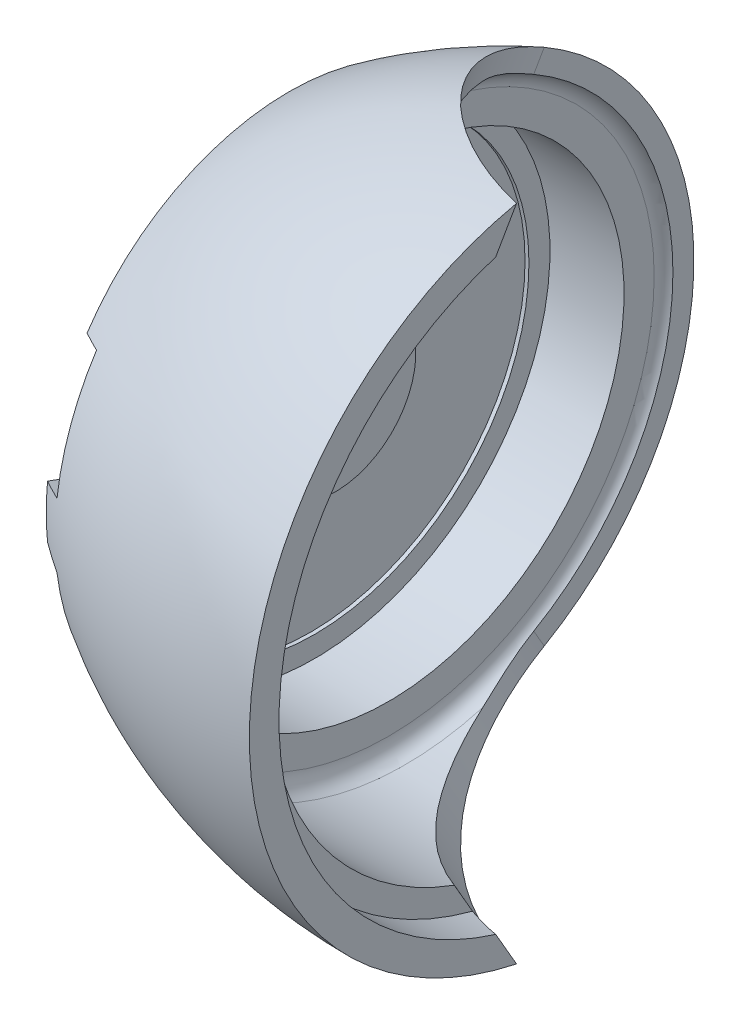
SolidWorks part; units mm, degrees
ref_plane "Front Plane" through (0, 0, 0) normal (0, 0, 1) x (1, 0, 0)
ref_plane "Top Plane" through (0, 0, 0) normal (0, 1, 0) x (1, 0, 0)
ref_plane "Right Plane" through (0, 0, 0) normal (1, 0, 0) x (0, 0, -1)
sketch "Sketch1" plane through (0, 0, 0) normal (0, 0, 1) x (1, 0, 0)
  line L0 (0, -55) -> (0, 55) construction
  line L1 (55, 0) -> (-55, 0) construction
  line L3 (-39.088, 0) -> (-39.088, 12.4)
  line L4 (-39.088, 12.4) -> (-42.39, 12.4)
  line L5 (-42.3, 33.02) -> (-42.3, 36.2585)
  line L7 (-42.988, 0) -> (-39.088, 0)
  line L9 (-30.9, 36.2585) -> (-42.3, 36.2585)
  line L10 (-46.2, 37.409) -> (-46.2, 8.59)
  line L14 (-30.9, 43.434) -> (-5.91, 43.434)
  line L17 (-46.2, 8.59) -> (-42.988, 8.59)
  line L18 (-42.988, 8.59) -> (-42.988, 0)
  line L19 (-42.3, 33.02) -> (-42.9, 33.02)
  line L20 (-42.9, 33.02) -> (-42.9, 12.4)
  line L21 (-42.9, 12.4) -> (-42.39, 12.4)
  line L22 (-30.9, 36.2585) -> (-30.9, 43.434)
  line L23 (-0.51, 51.8144) -> (-0.51, 47.244)
  line L24 (-0.51, 47.244) -> (-5.91, 47.244)
  line L25 (-5.91, 47.244) -> (-5.91, 43.434)
  arc A1 (-0.51, 51.8144) -> (-46.2, 37.409) centre (0, -29.464) ccw
  dimension "D1" = 81.28
  dimension "D2" = 43.434
  dimension "D3" = 46.2
  dimension "D4" = 12.4
  dimension "D5" = 7.112
  dimension "D6" = 11.4
  dimension "D7" = 29.464
  dimension "D8" = 3.9
  dimension "D9" = 36.2585
  dimension "D10" = 5.4
  dimension "D11" = 0.51
  dimension "D12" = 3.9
  dimension "D13" = 3.81
  dimension "D14" = 0.6
  dimension "D15" = 33.02
  dimension "D16" = 3.81
revolve "Revolve1" add sketch "Sketch1" angle 360 about L7
fillet "Fillet1" radius 2.54 1 edges at (-30.9, 0, 43.434)
ref_axis "Axis1" through (-48.7934, 0, 0) along (1, 0, 0)
ref_plane "Plane3" through (0, 0, 0) normal (0, -0.866, 0.5) x (1, 0, 0)
sketch "Sketch9" plane through (0, 0, 0) normal (0, -0.866, 0.5) x (1, 0, 0)
  line L0 (-48.7934, 0) -> (18.8214, 0) construction
  line L2 (0, -53.5869) -> (0, 53.5869) construction
  circle A0 centre (5.08, 0) radius 35.052
  dimension "D1" = 70.104
  dimension "D2" = 5.08
extrude "Cut-Extrude4" cut sketch "Sketch9" against normal blind 57.912
mirror "Mirror3" about plane through (0, 0, 0) normal (0, 1, 0) of "Cut-Extrude4"
ref_plane "Plane4" through (0, 0, 0) normal (0, -0.5, -0.866) x (1, 0, 0)
sketch "Sketch10" plane through (0, 0, 0) normal (0, -0.5, -0.866) x (1, 0, 0)
  line L1 (-29.972, -27.8884) -> (28.0432, -27.8884)
  line L2 (-29.972, -27.8884) -> (-29.972, -56.7179)
  line L3 (-29.972, -56.7179) -> (28.0432, -56.7179)
  line L4 (28.0432, -27.8884) -> (28.0432, -56.7179)
  line L5 (-29.972, -42.8569) -> (-29.972, -46.0881) construction
revolve "Cut-Revolve2" cut sketch "Sketch10" angle 120 about axis through (-48.7934, 0, 0) along (1, 0, 0) reverse direction yes
ref_plane "Plane5" through (0, 0, 0) normal (0, -0.342, -0.9397) x (1, 0, 0)
sketch "Sketch11" plane through (0, 0, 0) normal (0, -0.342, -0.9397) x (1, 0, 0)
  line L1 (-42.3, 8.89) -> (-47.38, 8.89)
  line L2 (-42.3, 8.89) -> (-42.3, -8.89)
  line L3 (-42.3, -8.89) -> (-47.38, -8.89)
  line L4 (-47.38, 8.89) -> (-47.38, -8.89)
  line L5 (-48.7934, 0) -> (18.8214, 0) construction
  line L6 (-42.3, -36.2585) -> (-42.3, 36.2585) construction
  point P6 (-42.3, 0)
  dimension "D1" = 5.08
  dimension "D2" = 17.78
extrude "Cut-Extrude5" cut sketch "Sketch11" against normal blind 31.75 from offset 31.75 offset against normal yes
fillet "Fillet2" radius 2.54 1 edges at (-42.9, 10.8591, 29.8352)
mirror "Mirror4" about plane through (0, 0, 0) normal (0, 1, 0) of "Cut-Extrude5"
